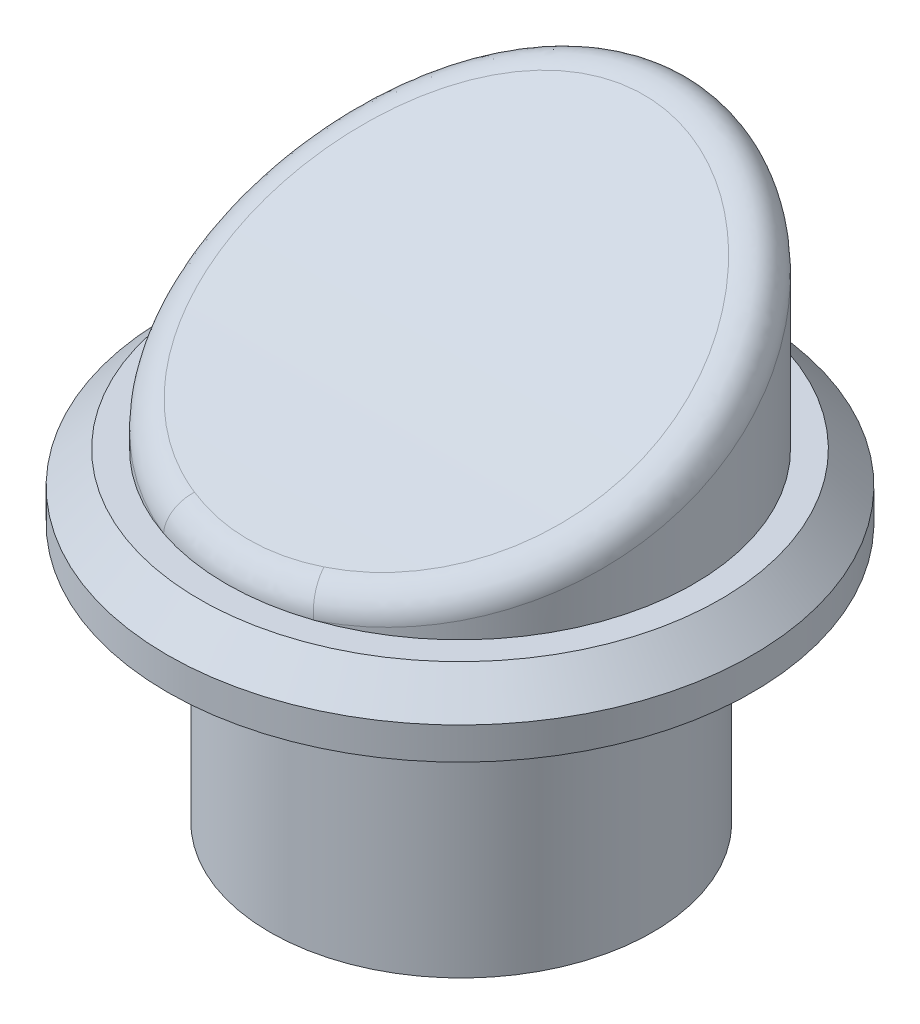
SolidWorks part; units mm, degrees
ref_plane "Front Plane" through (0, 0, 0) normal (0, 0, 1) x (1, 0, 0)
ref_plane "Top Plane" through (0, 0, 0) normal (0, 1, 0) x (1, 0, 0)
ref_plane "Right Plane" through (0, 0, 0) normal (1, 0, 0) x (0, 0, -1)
sketch "Sketch2" plane through (0, 0, 0) normal (0, 1, 0) x (1, 0, 0)
  line L1 (-9.3351, 9.5705) -> (9.3351, 9.5705)
  line L2 (-9.3351, 9.5705) -> (-9.3351, -9.5705)
  line L3 (-9.3351, -9.5705) -> (9.3351, -9.5705)
  line L4 (9.3351, 9.5705) -> (9.3351, -9.5705)
  line L5 (-9.3351, 9.5705) -> (9.3351, -9.5705) construction
  line L6 (-9.3351, -9.5705) -> (9.3351, 9.5705) construction
  point P0 (0, 0)
extrude "Boss-Extrude1" add sketch "Sketch2" along normal blind 10 and the other way blind 10
sketch "Sketch1" plane through (0, 0, 0) normal (0, 1, 0) x (1, 0, 0)
  line L4 (9.3351, -9.5705) -> (9.3351, 9.5705)
  line L5 (-9.3351, -9.5705) -> (9.3351, -9.5705)
  line L6 (-9.3351, 9.5705) -> (-9.3351, -9.5705)
  line L7 (9.3351, 9.5705) -> (-9.3351, 9.5705)
  line L8 (9.3351, -9.5705) -> (9.3351, 9.5705)
  line L9 (-9.3351, -9.5705) -> (9.3351, -9.5705)
  line L10 (-9.3351, 9.5705) -> (-9.3351, -9.5705)
  line L11 (9.3351, 9.5705) -> (-9.3351, 9.5705)
  circle A0 centre (0.063, -0.0235) radius 5.95
  dimension "D1" = 0
sketch "Sketch3" plane through (-9.3351, 0, 0) normal (-1, 0, 0) x (0, 0, 1)
  line L0 (-9.5235, 0) -> (9.5705, 0)
  line L2 (9.5705, -10) -> (9.5705, 10) construction
  line L3 (-9.5705, -10) -> (-9.5705, 10) construction
  line L4 (-9.5705, 9.4691) -> (-9.5235, 0)
  line L9 (9.5705, -10) -> (9.5705, 10)
  line L10 (9.5705, 10) -> (-9.5705, 10)
  line L11 (-9.5705, 10) -> (-9.5705, -10)
  line L12 (-9.5705, -10) -> (9.5705, -10)
  line L13 (9.5705, -10) -> (9.5705, 10)
  line L14 (9.5705, 10) -> (-9.5705, 10)
  line L15 (-9.5705, 10) -> (-9.5705, -10)
  line L16 (-9.5705, -10) -> (9.5705, -10)
  spline S0 degree 2 poles (9.5705, 0) (-1.0163, 2.6501) (-9.5705, 9.4691) knots 0 0 0 1 1 1
  point P0 (0, 3.4446)
  point P3 (0.0235, 0)
  line M1 (9.5705, -10) -> (9.5705, 10)
  line M2 (9.5705, 10) -> (-9.5705, 10)
  line M3 (-9.5705, 10) -> (-9.5705, -10)
  dimension "D1" = 0
extrude "Cut-Extrude1" cut sketch "Sketch3" against normal blind 20 contours S0 M1 M2 M3 region at (-9.3351, 6.3284, 2.4362)
sketch "Sketch5" plane through (0, -10, 0) normal (0, -1, 0) x (1, 0, 0)
  line L1 (-9.3351, 9.5705) -> (9.3351, 9.5705)
  line L2 (-9.3351, 9.5705) -> (-9.3351, -9.5705)
  line L3 (-9.3351, -9.5705) -> (9.3351, -9.5705)
  line L4 (9.3351, 9.5705) -> (9.3351, -9.5705)
  line L5 (-9.3351, 9.5705) -> (9.3351, -9.5705) construction
  line L6 (-9.3351, -9.5705) -> (9.3351, 9.5705) construction
  circle A0 centre (0, 0) radius 9.1024
extrude "Cut-Extrude3" cut sketch "Sketch5" against normal blind 20
extrude "Cut-Extrude4" cut sketch "Sketch1" against normal blind 20
sketch "Sketch6" plane through (0, 0, 0) normal (0, -1, 0) x (1, 0, 0)
  circle A1 centre (0, 0) radius 9.1024
  circle A2 centre (0, 0) radius 9.1024
  dimension "D1" = 0
extrude "Boss-Extrude2" add sketch "Sketch6" along normal blind 2
sketch "Sketch7" plane through (0, -2, 0) normal (0, -1, 0) x (1, 0, 0)
  circle A0 centre (0, 0) radius 7.2697
  circle A1 centre (0, 0) radius 9.1024
  circle A2 centre (0, 0) radius 9.1024
  dimension "D1" = 0
extrude "Cut-Extrude8" cut sketch "Sketch7" against normal through all from offset 2 offset against normal yes
chamfer "Chamfer1" distance 1 angle 45 1 edges at (0, 0, -9.1024)
fillet "Fillet1" radius 1 1 edges at (1.4592, 0.677, 7.1217)
